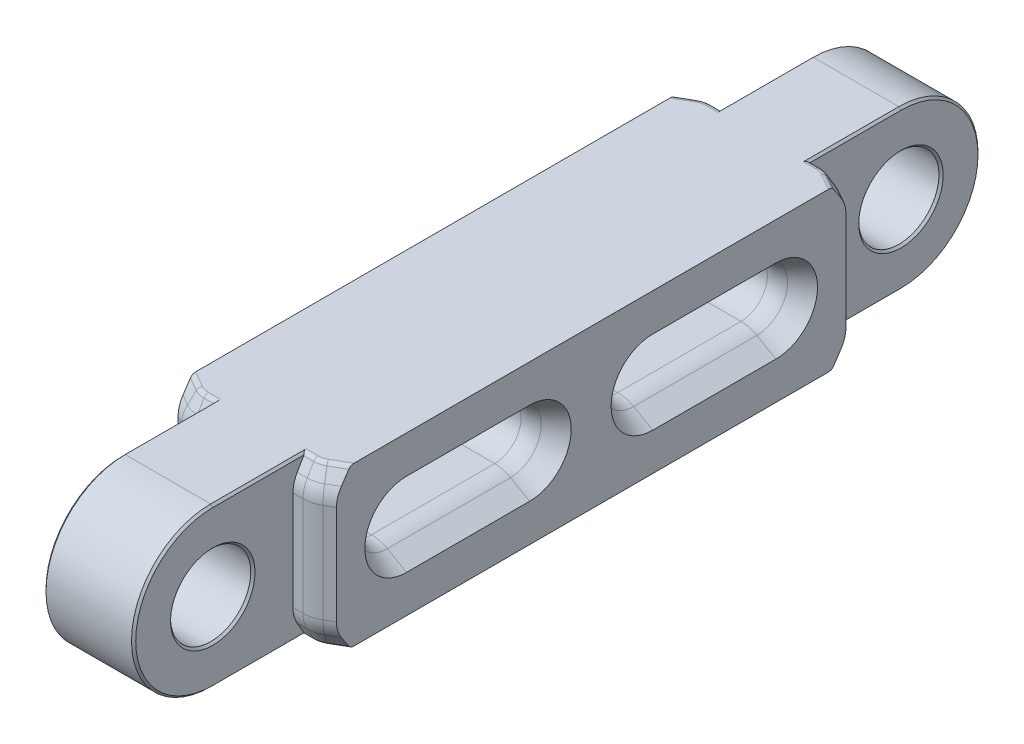
SolidWorks part; units mm, degrees
ref_plane "Front Plane" through (0, 0, 0) normal (1, 0, 0) x (0, 1, 0)
ref_plane "Top Plane" through (0, 0, 0) normal (0, 0, 1) x (0, 1, 0)
ref_plane "Right Plane" through (0, 0, 0) normal (0, 1, 0) x (-1, 0, 0)
sketch "Sketch1" plane through (0, 0, 0) normal (1, 0, 0) x (0, 1, 0)
  line L0 (-15, 0) -> (-15, -130.4)
  line L1 (-15, -65.2) -> (15, -65.2) construction
  line L2 (15, -130.4) -> (15, 0)
  line L3 (-5, -30.2) -> (-5, -53.5333)
  line L4 (-15, -115.2) -> (15, -115.2)
  line L6 (-15, -15.2) -> (15, -15.2)
  line L7 (0, 15) -> (0, -65.2)
  circle A0 centre (0, 0) radius 7.6
  circle A1 centre (0, 0) radius 15
  circle A26 centre (0, -130.4) radius 15
  circle A27 centre (0, -130.4) radius 7.6
  circle A28 centre (0, -53.5333) radius 5
  circle A29 centre (0, -30.2) radius 5
  point P16 (-5, -53.5333)
  point P17 (0, -58.5333)
  point P20 (0, -25.2)
  dimension "D1" = 30
  dimension "D2" = 15.2
  dimension "D3" = 15.2
  dimension "D4" = 100
  dimension "D5" = 10
  dimension "D6" = 6.6667
  dimension "D7" = 10
extrude "Boss-Extrude1" add sketch "Sketch1" along normal blind 8.5 contours L7 A1 A0 | A1 L0 L6 L7 | L0 L1 L7 L6 region at (0, -11.4068, -11.8513) region at (0, -10.3694, 10.3694) region at (0, -8.8374, -39.7625)
extrude "Boss-Extrude2" add sketch "Sketch1<4>" along normal blind 15 contours L0 L1 L7 L6 region at (0, -8.8374, -39.7625)
sketch "Sketch1<4>" plane through (0, 0, 0) normal (1, 0, 0) x (0, 1, 0) same geometry as "Sketch1"
chamfer "Chamfer8" distance 3 angle 30 1 edges at (15, -7.5, -15.2) first distance on face at (11.75, -7.5, -15.2)
fillet "Fillet6" radius 6 1 edges at (12, -7.5, -15.2)
chamfer "Chamfer9" distance 4 angle 30 3 edges at (14.1962, -15, -16.4679) (11.9452, -15, -15.4044) (9.4462, -15, -15.2) first distance on face at (14.1962, -7.5, -16.4679) first distance on face at (11.9188, -7.5, -15.5032) first distance on face at (9.4462, -7.5, -15.2)
fillet "Fillet7" radius 6 3 edges at (14.1962, -11, -16.4679) (11.9452, -11, -15.4044) (9.4462, -11, -15.2)
chamfer "Chamfer10" distance 5 angle 30 3 edges at (15, -3.5355, -57.0689) (15, -5, -41.8667) (15, -3.5355, -26.6645) first distance on face at (7.5, -3.0178, -56.5511) first distance on face at (7.5, -5, -41.8667) first distance on face at (7.5, -3.0178, -27.1822)
fillet "Fillet8" radius 6 3 edges at (10, -3.5355, -57.0689) (10, -5, -41.8667) (10, -3.5355, -26.6645)
fillet "Fillet9" radius 1 3 edges at (9.4462, -15, -17.5094) (11.3475, -15, -17.6352) (13.6188, -15, -18.8013)
chamfer "Chamfer11" distance 0.4 angle 45 3 edges at (8.5, -7.6, 0) (8.5, -15, -9.0434) (8.5, -10.6066, 10.6066)
mirror "Mirror1" about plane through (8.5, 0, 0) normal (0, 1, 0) of bodies 102
mirror "Mirror2" about plane through (8.5, 0, -65.2) normal (0, 0, 1) of bodies 108
mirror "Mirror3" about plane through (0, 0, 0) normal (1, 0, 0) of bodies 109
equation "\"D6@Sketch1\"=\"D5@Sketch1\"*2/3"
equation "\"D7@Sketch1\"=\"D5@Sketch1\""
